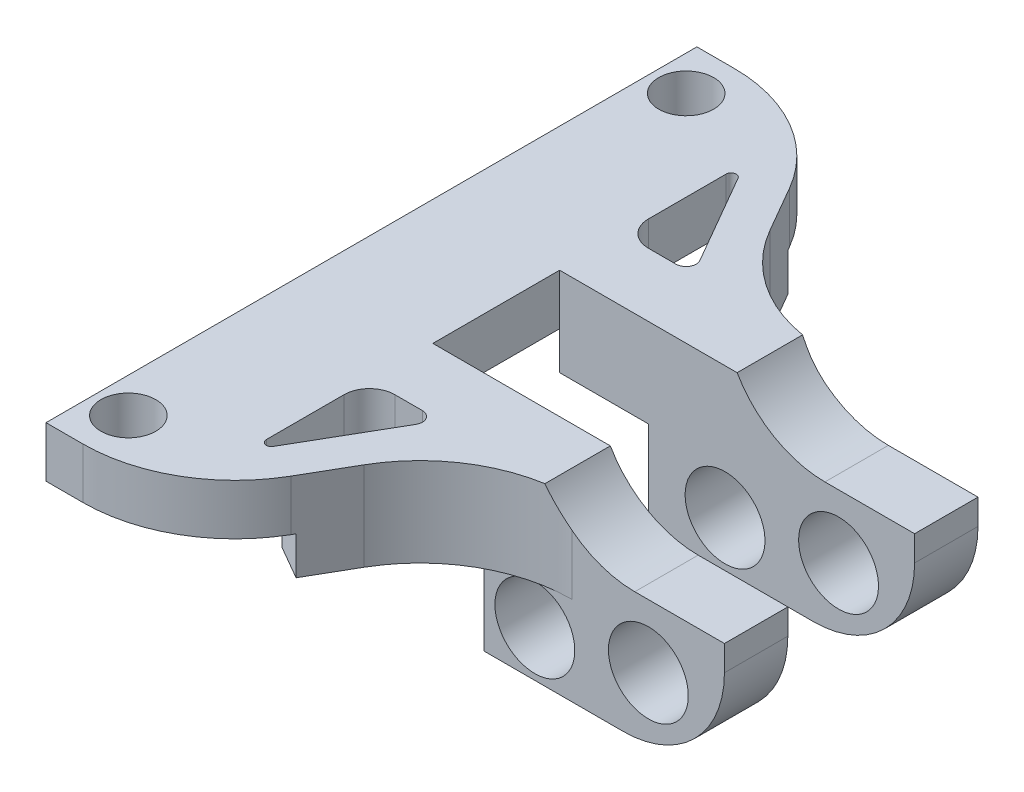
SolidWorks part; units mm, degrees
ref_plane "Front Plane" through (0, 0, 0) normal (0, 0, 1) x (1, 0, 0)
ref_plane "Top Plane" through (0, 0, 0) normal (0, 1, 0) x (1, 0, 0)
ref_plane "Right Plane" through (0, 0, 0) normal (1, 0, 0) x (0, 0, -1)
sketch "Sketch1" plane through (0, 0, 0) normal (0, 1, 0) x (1, 0, 0)
  line L0 (4.5, 30.226) -> (10.6074, 19.6478)
  line L1 (0, 2.375) -> (4.5, 2.375)
  line L2 (0, 2.375) -> (0, -2.375)
  line L3 (0, -2.375) -> (4.5, -2.375)
  line L4 (4.5, 2.375) -> (4.5, -2.375)
  line L5 (0, 2.375) -> (-1.75, 2.375)
  line L6 (0, 2.375) -> (0, -2.375)
  line L7 (0, -2.375) -> (-1.75, -2.375)
  line L8 (-1.75, 2.375) -> (-1.75, -2.375)
  line L9 (-1.75, 2.375) -> (4.5, 2.375)
  line L10 (-1.75, 2.375) -> (-1.75, 30.226)
  line L11 (-1.75, 30.226) -> (4.5, 30.226)
  line L12 (4.5, 2.375) -> (4.5, 30.226)
  line L13 (4.5, 30.226) -> (2.8376, 29.2662)
  line L14 (10.6074, 19.6478) -> (8.945, 18.688)
  line L15 (2.8376, 29.2662) -> (8.945, 18.688)
  line L20 (4.5, -2.375) -> (10.6074, 8.2032)
  line L21 (4.5, -2.375) -> (2.8376, -1.4152)
  line L22 (10.6074, 8.2032) -> (8.945, 9.163)
  line L23 (2.8376, -1.4152) -> (8.945, 9.163)
  line L24 (5.135, 2.5639) -> (6.7974, 1.6041)
  line L25 (4.5, 7.5755) -> (13.39, 7.5755)
  line L26 (4.5, 7.5755) -> (4.5, 10.7505)
  line L27 (4.5, 10.7505) -> (13.39, 10.7505)
  line L28 (13.39, 7.5755) -> (13.39, 10.7505)
  line L29 (4.5, 7.5755) -> (13.39, 10.7505) construction
  line L30 (4.5, 10.7505) -> (13.39, 7.5755) construction
  line L31 (4.5, 17.1005) -> (13.39, 17.1005)
  line L32 (4.5, 17.1005) -> (4.5, 20.2755)
  line L33 (4.5, 20.2755) -> (13.39, 20.2755)
  line L34 (13.39, 17.1005) -> (13.39, 20.2755)
  line L35 (4.5, 17.1005) -> (13.39, 20.2755) construction
  line L36 (4.5, 20.2755) -> (13.39, 17.1005) construction
  line L37 (0, 2.375) -> (0, 30.226) construction
  line L38 (5.135, 25.2871) -> (7.6421, 26.7346)
  line L39 (8.945, 20.2755) -> (8.945, 17.1005)
  line L40 (8.945, 10.7505) -> (8.945, 7.5755)
  line L42 (13.39, 20.2755) -> (22.28, 20.2755)
  line L43 (13.39, 20.2755) -> (13.39, 17.1005)
  line L44 (13.39, 17.1005) -> (22.28, 17.1005)
  line L45 (22.28, 20.2755) -> (22.28, 17.1005)
  line L46 (13.39, 10.7505) -> (22.28, 10.7505)
  line L47 (13.39, 10.7505) -> (13.39, 7.5755)
  line L48 (13.39, 7.5755) -> (22.28, 7.5755)
  line L49 (22.28, 10.7505) -> (22.28, 7.5755)
  circle A0 centre (0, 0) radius 1.375
  circle A1 centre (0, 27.94) radius 1.375
  point P7 (0, 0)
  dimension "D1" = 2.75
  dimension "D6" = 2.75
  dimension "D11" = 1.75
  dimension "D16" = 8.89
  dimension "D2" = 1.75
  dimension "D3" = 4.75
  dimension "D4" = 6.25
  dimension "D5" = 2.286
  dimension "D7" = 27.94
  dimension "D8" = 60
  dimension "D9" = 60
  dimension "D10" = 6.35
  dimension "D12" = 3.175
  dimension "D13" = 8.89
  dimension "D14" = 7.62
  dimension "D15" = 7.62
extrude "Boss-Extrude1" add sketch "Sketch1" along normal blind 2.54 contours A0 L2 L5 L8 L7 | A0 L2 L3 L4 L1 | L15 L13 L11 L10 L5 L1 L12 | L15 L0 L12 | L15 L14 | L13 L15 L12 | L25 L23 L12 L4 L20 | L23 L21 L4 L9 | L23 L9 L12 | L23 L25 L20 L22 | L25 L28 L27 L26 L23 L22 L20 | L33 L32 L31 L12 | L40 L27 L12 L25 L23 | L32 L33 L34 L31 | L20 L21 L23 L22 | L0 L13 L15 L14 region at (1.3748, 0, -15.6429) region at (5.3116, 0, -27.2634) region at (3.9459, 0, -28.6264) region at (-0.875, 0, -2.3244) region at (6.6183, 0, -18.6305) region at (8.6395, 0, -19.7463) region at (2.2196, 0, -0.1626) region at (6.6183, 0, -9.2205) region at (3.9459, 0, 0.7754) region at (11.3859, 0, -9.2989) region at (7.5797, 0, -4.8228) region at (9.6015, 0, -8.1889)
extrude "Boss-Extrude3" add sketch "Sketch1<3>" against normal blind 1.905 contours L27 L40 L22 L20 L25 L28 | L40 L27 L12 L25 L23 | L25 L23 L24 L20 | L22 L40 L25 L20 | L40 L23 L25 | L14 L39 L31 L34 L33 L0 | L39 L15 L33 L12 L31 | L39 L33 L15 | L33 L39 L14 L0 | L38 L15 L33 L0 region at (7.5797, 0, -23.0282) region at (11.3859, 0, -18.5521) region at (9.6015, 0, -19.6621) region at (6.6183, 0, -18.6305) region at (8.6395, 0, -19.7463) region at (6.6183, 0, -9.2205) region at (11.3859, 0, -9.2989) region at (7.5797, 0, -4.8228) region at (8.6395, 0, -8.1047) region at (9.6015, 0, -8.1889)
sketch "Sketch1<3>" plane through (0, 0, 0) normal (0, 1, 0) x (1, 0, 0) same geometry as "Sketch1"
extrude "Boss-Extrude4" add sketch "Sketch1<4>" against normal blind 6.35 contours L25 L28 L27 L12 L23 L22 L20 | L31 L34 L33 L0 L14 L15 L12 | L45 L42 L34 L44 | L49 L46 L28 L48 region at (11.3859, 0, -18.5521) region at (17.835, 0, -18.688) region at (11.3859, 0, -9.2989) region at (17.835, 0, -9.163)
sketch "Sketch1<4>" plane through (0, 0, 0) normal (0, 1, 0) x (1, 0, 0) same geometry as "Sketch1"
sketch "Sketch2" plane through (0, 0, -20.2755) normal (0, 0, -1) x (-1, 0, 0)
  line L0 (-11.8175, 2.54) -> (-11.8175, -6.35) construction
  line L1 (-10.2449, 2.54) -> (-13.39, 2.54) construction
  line L2 (-10.2449, -6.35) -> (-22.28, -6.35) construction
  circle A0 centre (-11.8175, 0.7148) radius 0.7744
  circle A1 centre (-11.8175, -3.6002) radius 2
  point P10 (-11.8175, -3.6002)
  point P11 (-11.8175, 0.7148)
  dimension "D1" = 4
fillet "Fillet1" radius 5.08 2 edges at (13.39, 0, -9.163) (13.39, 0, -18.688)
fillet "Fillet3" radius 7.62 2 edges at (10.2449, 0.3175, -7.5755) (10.2449, 0.3175, -20.2755)
fillet "Fillet4" radius 7.62 2 edges at (4.5, 1.27, 2.375) (4.5, 1.27, -30.226)
fillet "Fillet6" radius 2.54 2 edges at (10.6074, -4.1275, -19.6478) (10.6074, -4.1275, -8.2032)
fillet "Fillet8" [suppressed] radius 5.08
fillet "Fillet9" radius 1.27 2 edges at (4.5, 1.27, -20.2755) (4.5, 1.27, -7.5755)
fillet "Fillet10" radius 0.508 2 edges at (8.0285, 0.3175, -20.2755) (8.0285, 0.3175, -7.5755)
fillet "Fillet11" radius 0.254 2 edges at (4.5, 1.27, -26.387) (4.5, 1.27, -1.464)
fillet "Fillet12" radius 5.08 2 edges at (22.28, -6.35, -9.163) (22.28, -6.35, -18.688)
sketch "Sketch3" plane through (0, 0, -20.2755) normal (0, 0, -1) x (-1, 0, 0)
  line L0 (-10.2449, -6.35) -> (-10.2449, -1.905) construction
  line L1 (-10.2449, -6.35) -> (-17.2, -6.35) construction
  line L2 (-17.7894, 0) -> (-22.28, 0) construction
  line L3 (-22.28, -1.27) -> (-22.28, 0) construction
  circle A0 centre (-12.7849, -4.0551) radius 2
  circle A1 centre (-18.47, -3.175) radius 2
  dimension "D1" = 4
  dimension "D2" = 4
  dimension "D3" = 2.54
  dimension "D4" = 2.2949
  dimension "D6" = 3.81
  dimension "D5" = 3.175
extrude "Cut-Extrude1" cut sketch "Sketch3" against normal through all
